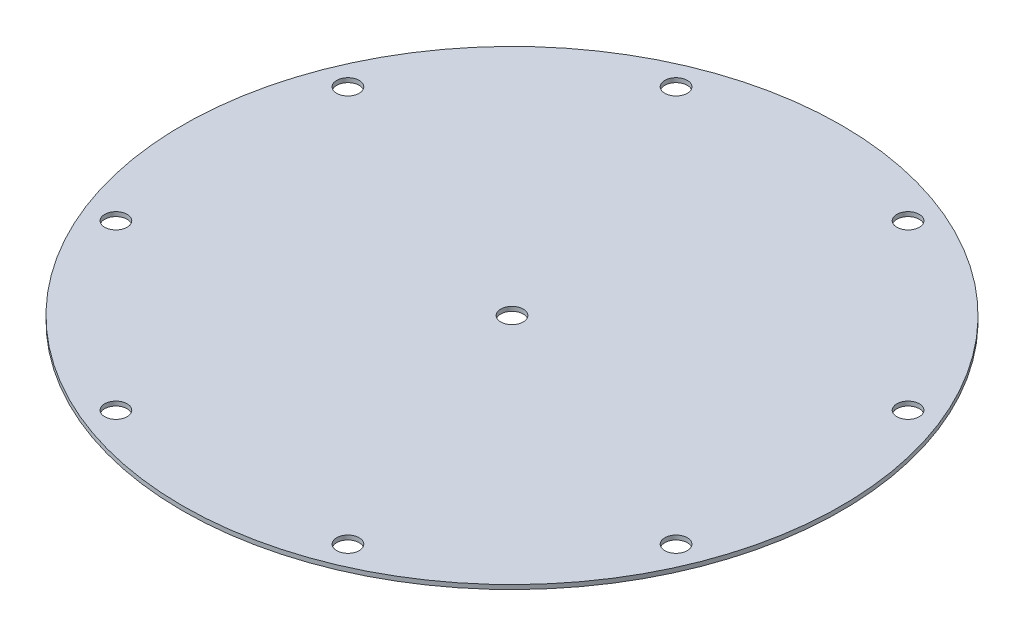
SolidWorks part; units mm, degrees
ref_plane "Front Plane" through (0, 0, 0) normal (0, 0, 1) x (1, 0, 0)
ref_plane "Top Plane" through (0, 0, 0) normal (0, 1, 0) x (1, 0, 0)
ref_plane "Right Plane" through (0, 0, 0) normal (1, 0, 0) x (0, 0, -1)
sketch "Sketch2" plane through (0, 0, 0) normal (1, 0, 0) x (0, 0, -1)
  line L0 (0, 0) -> (-76.0999, 0)
  line L1 (-76.0999, 0) -> (-76.0999, 1)
  line L2 (-76.0999, 1) -> (0, 1)
  line L5 (0, 1) -> (0, 0)
  dimension "D1" = 76.0999
  dimension "D2" = 1
ref_axis "Axis1" through (0, -0.05, 0) along (0, 1, 0)
revolve "Revolve1" add sketch "Sketch2" angle 360 about axis through (0, -0.05, 0) along (0, 1, 0)
hole_wizard "#6 (0.204) Diameter Hole1" positions "Sketch6" profile "Sketch7" hole size "#6" standard "ANSI Inch" end condition through all
sketch "Sketch6" plane through (0, 1, 0) normal (0, 1, 0) x (1, 0, 0)
  line L0 (0, 0) -> (-53.438, 129.0108) construction
  line L2 (0, 0) -> (0, 109.0908) construction
  point P0 (-26.7878, 64.6716)
  dimension "D1" = 22.5
  dimension "D2" = 70
sketch "Sketch7" plane through (-26.7878, 1, -64.6716) normal (1, 0, 0) x (0, 0, 1)
  line L0 (0, 0) -> (0, 1)
  line L1 (0, 1) -> (2.5908, 1)
  line L2 (2.5908, 1) -> (2.5908, 0)
  line L5 (2.5908, 0) -> (0, 0)
  line L11 (0, -6.35) -> (0, 107.95) construction
  dimension "Thru Hole Dia." = 5.1816
  dimension "Thru Hole Depth" = 1
pattern_circular "CirPattern3" count 8 over 360 about axis through (0, -0.05, 0) along (0, 1, 0) of "#6 (0.204) Diameter Hole1"
hole_wizard "#6 (0.204) Diameter Hole2" positions "Sketch8" profile "Sketch9" hole size "#6" standard "ANSI Inch" end condition through all
sketch "Sketch8" plane through (0, 1, 0) normal (0, 1, 0) x (1, 0, 0)
  line L0 (0, 0) -> (106.3094, -1.7118) construction
  point P7 (0, 0)
sketch "Sketch9" plane through (0, 1, 0) normal (1, 0, 0) x (0, 0, 1)
  line L0 (0, 0) -> (0, 1)
  line L1 (0, 1) -> (2.5908, 1)
  line L2 (2.5908, 1) -> (2.5908, 0)
  line L5 (2.5908, 0) -> (0, 0)
  line L11 (0, -6.35) -> (0, 107.95) construction
  dimension "Thru Hole Dia." = 5.1816
  dimension "Thru Hole Depth" = 1
equation "\"TubeDiameter\" = 6.5433in"
equation "\"D1@Sketch2\"=\"TubeDiameter\"/2-7mm"
